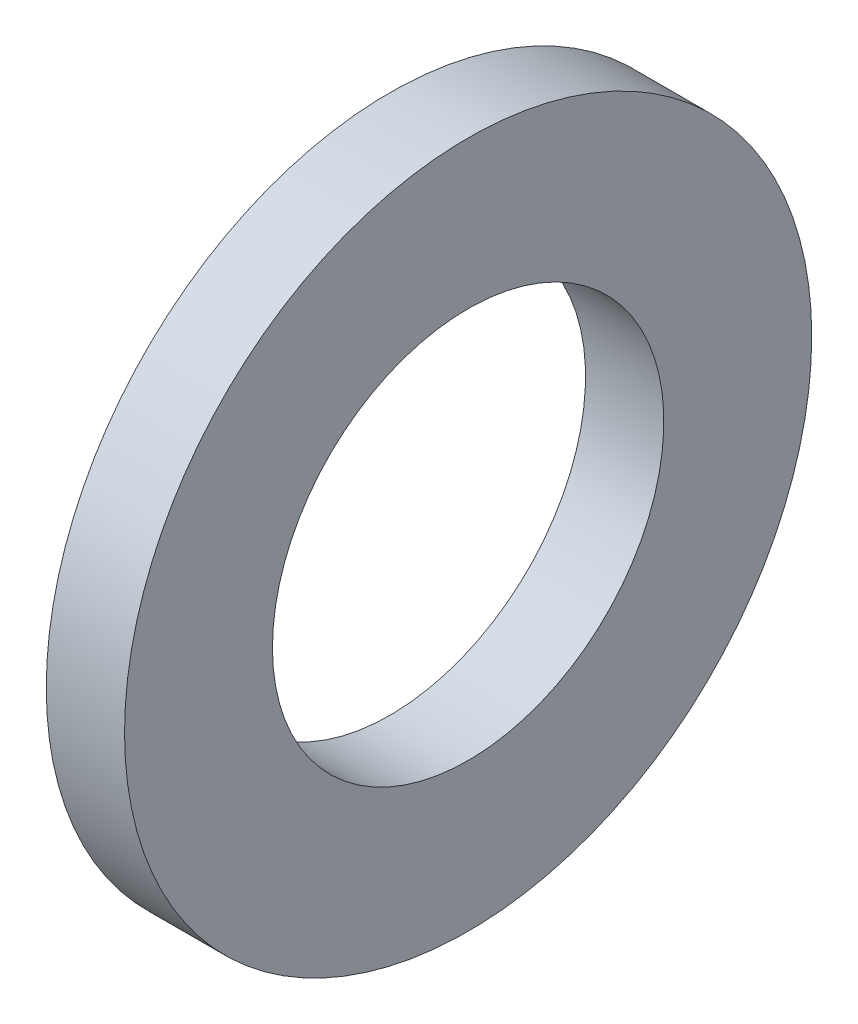
SolidWorks part; units mm, degrees
ref_plane "Front Plane" through (0, 0, 0) normal (0, 0, 1) x (1, 0, 0)
ref_plane "Top Plane" through (0, 0, 0) normal (0, 1, 0) x (1, 0, 0)
ref_plane "Right Plane" through (0, 0, 0) normal (1, 0, 0) x (0, 0, -1)
sketch "Sketch2" plane through (0, 0, 0) normal (0, 0, 1) x (1, 0, 0)
  line L0 (0, 0) -> (58.591, 0) construction
  line L2 (0, 0) -> (18.4, 0)
  line L3 (0, 0) -> (0, 2.5)
  line L4 (0, 2.5) -> (18.4, 2.5)
  line L5 (18.4, 0) -> (18.4, 2.5)
  line L6 (6.0094, 2.5) -> (6.0094, 6)
  line L11 (6.0094, 6) -> (9.9794, 6)
  line L16 (12.9794, 6) -> (12.9794, 3)
  line L17 (12.9794, 3) -> (13.6398, 3)
  line L18 (13.6398, 3) -> (13.6398, 2.5)
  line L19 (13.6398, 2.5) -> (6.0094, 2.5)
  line L22 (13.6398, 2.5) -> (16.1198, 2.5)
  line L23 (13.6398, 2.5) -> (13.6398, 4)
  line L24 (13.6398, 4) -> (16.1198, 4)
  line L25 (16.1198, 2.5) -> (16.1198, 4)
  line L27 (6.0094, 6) -> (9.9794, 6)
  line L28 (6.0094, 6) -> (6.0094, 9)
  line L29 (6.0094, 9) -> (9.9794, 9)
  line L30 (9.9794, 6) -> (9.9794, 9)
  line L31 (6.0094, 9) -> (6.0094, 8.25)
  line L32 (6.0094, 8.25) -> (5.0094, 8.25)
  line L33 (8.6609, 22.001) -> (8.6609, 12.476) construction
  line L34 (5.0094, 12.476) -> (12.3124, 12.476)
  line L35 (9.9794, 9) -> (12.3124, 9)
  line L36 (5.0094, 7.9375) -> (1.8344, 7.9375)
  line L37 (5.0094, 8.25) -> (5.0094, 12.476)
  line L38 (5.0094, 7.9375) -> (5.0094, 13.9365)
  line L39 (5.0094, 13.9365) -> (1.8344, 13.9365)
  line L40 (1.8344, 7.9375) -> (1.8344, 13.9365)
  line L41 (5.0094, 22.001) -> (12.3124, 22.001)
  line L42 (5.0094, 22.001) -> (5.0094, 30.1625)
  line L43 (5.0094, 30.1625) -> (12.3124, 30.1625)
  line L44 (12.3124, 22.001) -> (12.3124, 30.1625)
  line L49 (16.6398, 22.001) -> (16.6398, 7.5)
  line L51 (23.0198, 7.5) -> (23.0198, 6.5)
  line L54 (16.1198, 4) -> (13.6398, 4)
  line L56 (18.0398, 7.5) -> (23.0198, 7.5)
  line L57 (13.3124, 22.001) -> (16.6398, 22.001)
  line L58 (16.1198, 3.5) -> (20.0198, 3.5)
  line L59 (29.9098, 14) -> (26.9098, 11)
  line L60 (4.0094, 31.75) -> (18.0398, 31.75)
  line L61 (18.0398, 7.5) -> (23.0198, 7.5)
  line L62 (18.0398, 7.5) -> (18.0398, 12)
  line L63 (18.0398, 12) -> (23.0198, 12)
  line L64 (23.0198, 7.5) -> (23.0198, 12)
  line L65 (18.0398, 31.75) -> (18.0398, 12)
  line L66 (23.0198, 11) -> (26.9098, 11)
  line L67 (34.8098, 23) -> (31.3098, 19.5)
  line L68 (35.8098, 31) -> (38.7998, 33.99)
  line L69 (29.9098, 14) -> (29.9098, 15)
  line L70 (29.9098, 15) -> (22.9398, 15)
  line L71 (22.9398, 15) -> (21.0398, 15)
  line L72 (18.0398, 7.5) -> (16.6398, 7.5)
  line L73 (21.0398, 15) -> (21.0398, 43)
  line L74 (19.5798, 40) -> (9.6198, 40)
  line L75 (9.6198, 40) -> (4.0094, 40)
  line L76 (21.0398, 43) -> (19.5798, 43)
  line L77 (22.9398, 15) -> (29.9098, 15)
  line L78 (22.9398, 15) -> (22.9398, 21)
  line L79 (22.9398, 21) -> (29.9098, 21)
  line L80 (29.9098, 15) -> (29.9098, 21)
  line L81 (9.6198, 40) -> (19.5798, 40)
  line L82 (9.6198, 40) -> (9.6198, 50)
  line L83 (9.6198, 50) -> (19.5798, 50)
  line L84 (19.5798, 40) -> (19.5798, 50)
  line L85 (4.0094, 40) -> (4.0094, 31.75)
  line L86 (12.9794, 3) -> (12.9794, 2.5)
  line L87 (31.3098, 19.5) -> (29.9098, 19.5)
  line L88 (21.4694, 63.5) -> (21.4694, 51.308)
  line L89 (21.4694, 63.5) -> (25.9398, 63.5)
  line L90 (25.9398, 63.5) -> (25.9398, 25)
  line L91 (27.8398, 25) -> (25.9398, 25)
  line L92 (9.6198, 48) -> (8.1598, 48)
  line L93 (8.1598, 48) -> (8.1598, 53.476)
  line L94 (8.1598, 53.476) -> (19.5798, 53.476)
  line L95 (19.5798, 53.476) -> (19.5798, 50)
  line L96 (13.8698, 63.001) -> (13.8698, 53.476) construction
  line L97 (8.1598, 63.001) -> (19.5798, 63.001)
  line L98 (8.1598, 63.001) -> (8.1598, 68.2625)
  line L99 (8.1598, 68.2625) -> (19.5798, 68.2625)
  line L100 (19.5798, 63.001) -> (19.5798, 68.2625)
  line L101 (12.9794, 6) -> (11.9794, 6)
  line L102 (8.1598, 44.825) -> (4.9848, 44.825)
  line L103 (8.1598, 44.825) -> (8.1598, 54.9365)
  line L104 (8.1598, 54.9365) -> (4.9848, 54.9365)
  line L106 (9.9794, 6) -> (10.8794, 6)
  line L107 (27.8398, 25) -> (34.8098, 25)
  line L108 (34.8098, 25) -> (34.8098, 23)
  line L109 (0, 0) -> (-2, 0)
  line L110 (0, 0) -> (0, 11)
  line L111 (27.8398, 25) -> (34.8098, 25)
  line L112 (27.8398, 25) -> (27.8398, 32.5)
  line L113 (27.8398, 32.5) -> (34.8098, 32.5)
  line L114 (34.8098, 25) -> (34.8098, 32.5)
  line L115 (35.8098, 31) -> (34.8098, 31)
  line L116 (27.8398, 32.5) -> (27.8398, 64.5)
  line L117 (20.5373, 74.025) -> (6.2023, 74.025)
  line L118 (6.2023, 74.025) -> (6.2023, 76.2)
  line L119 (38.7998, 47.29) -> (30.8398, 55.25)
  line L120 (0, 11) -> (-2, 11)
  line L121 (38.7998, 43.815) -> (30.8623, 43.815)
  line L123 (-4.8152, 69.85) -> (1.5348, 76.2)
  line L124 (38.7998, 47.29) -> (38.7998, 33.99)
  line L125 (-2, 0) -> (-2, 11)
  line L126 (38.7998, 37.465) -> (30.8623, 37.465)
  line L127 (30.8623, 43.815) -> (30.8623, 37.465)
  line L128 (6.0094, 2.5) -> (6.0094, 0)
  line L129 (-0.0152, 63.5) -> (-0.0152, 30)
  line L132 (4.9848, 63.5) -> (-0.0152, 63.5)
  line L136 (-1.8152, 30) -> (-11.7752, 30)
  line L138 (-13.7752, 25.4) -> (-2, 25.4)
  line L139 (-2, 25.4) -> (-2, 11.5)
  line L140 (27.8398, 64.5) -> (20.5373, 64.5)
  line L141 (-1.8152, 30) -> (-11.7752, 30)
  line L142 (-1.8152, 30) -> (-1.8152, 39)
  line L143 (-1.8152, 39) -> (-11.7752, 39)
  line L144 (-11.7752, 30) -> (-11.7752, 39)
  line L145 (20.5373, 64.5) -> (20.5373, 74.025)
  line L146 (-12.7752, 37) -> (-12.7752, 47.29)
  line L147 (-12.7752, 37) -> (-11.7752, 37)
  line L148 (30.8398, 55.25) -> (30.8398, 76.2)
  line L149 (11.9794, 6) -> (11.9794, 5.45)
  line L154 (-2, 11.5) -> (0.5, 11.5)
  line L155 (4.9848, 60.6197) -> (24.0348, 60.6197)
  line L160 (4.9848, 60.6197) -> (4.9848, 55.8572)
  line L161 (4.9848, 55.8572) -> (24.0348, 55.8572)
  line L166 (24.0348, 60.6197) -> (24.0348, 55.8572)
  line L167 (4.9848, 60.6197) -> (24.0348, 55.8572) construction
  line L172 (4.9848, 55.8572) -> (24.0348, 60.6197) construction
  line L173 (24.0348, 62.2072) -> (25.9398, 62.2072)
  line L174 (11.9794, 5.45) -> (10.8794, 5.45)
  line L175 (10.8794, 6) -> (10.8794, 5.45)
  line L176 (24.0348, 62.2072) -> (24.0348, 54.2697)
  line L177 (24.0348, 54.2697) -> (25.9398, 54.2697)
  line L178 (25.9398, 62.2072) -> (25.9398, 54.2697)
  line L179 (24.0348, 62.2072) -> (25.9398, 54.2697) construction
  line L180 (24.0348, 54.2697) -> (25.9398, 62.2072) construction
  line L181 (3, 19.6197) -> (15.7, 19.6197)
  line L182 (3, 19.6197) -> (3, 14.8572)
  line L183 (3, 14.8572) -> (15.7, 14.8572)
  line L184 (15.7, 19.6197) -> (15.7, 14.8572)
  line L185 (3, 19.6197) -> (15.7, 14.8572) construction
  line L186 (3, 14.8572) -> (15.7, 19.6197) construction
  line L187 (15.7, 21.2072) -> (16.6398, 21.2072)
  line L188 (15.7, 21.2072) -> (15.7, 13.2697)
  line L189 (15.7, 13.2697) -> (16.6398, 13.2697)
  line L190 (16.6398, 21.2072) -> (16.6398, 13.2697)
  line L191 (15.7, 21.2072) -> (16.6398, 13.2697) construction
  line L192 (15.7, 13.2697) -> (16.6398, 21.2072) construction
  line L193 (0.5, 11.5) -> (0.5, 6.9375)
  line L194 (0.5, 6.9375) -> (1.8344, 6.9375)
  line L195 (23.0198, 6.5) -> (20.0198, 3.5)
  line L196 (4.9848, 63.5) -> (4.9848, 54.9365)
  line L197 (3, 43.825) -> (4.9848, 43.825)
  line L198 (1.8344, 6.9375) -> (1.8344, 7.9375)
  line L199 (6.0094, 0) -> (12.9794, 0)
  line L200 (12.9794, 0) -> (12.9794, 2.5)
  line L201 (18.0398, 31.75) -> (18.0398, 35.875)
  line L202 (18.0398, 35.875) -> (21.0398, 35.875)
  line L203 (30.8398, 76.2) -> (6.2023, 76.2)
  line L204 (2.7573, 69.85) -> (7.2023, 69.85) construction
  line L205 (7.2023, 67.4688) -> (26.2523, 67.4688)
  line L206 (7.2023, 74.025) -> (7.2023, 64.5)
  line L207 (7.2023, 64.5) -> (-1.8152, 64.5)
  line L208 (-1.8152, 64.5) -> (-1.8152, 39)
  line L209 (-12.7752, 47.29) -> (-4.8152, 55.25)
  line L210 (-4.8152, 55.25) -> (-4.8152, 69.85)
  line L211 (7.2023, 67.4688) -> (7.2023, 72.2312)
  line L212 (7.2023, 72.2312) -> (26.2523, 72.2313)
  line L213 (26.2523, 67.4688) -> (26.2523, 72.2313)
  line L214 (26.2523, 73.8187) -> (30.8398, 73.8187)
  line L215 (26.2523, 73.8187) -> (26.2523, 65.8813)
  line L216 (26.2523, 65.8813) -> (30.8398, 65.8813)
  line L217 (30.8398, 73.8187) -> (30.8398, 65.8813)
  line L218 (2.7573, 72.2313) -> (24.9823, 72.2313)
  line L219 (2.7573, 72.2313) -> (2.7573, 67.4687)
  line L220 (2.7573, 67.4687) -> (24.9823, 67.4687)
  line L221 (24.9823, 72.2313) -> (24.9823, 67.4687)
  line L222 (24.9823, 69.85) -> (20.5373, 69.85) construction
  line L223 (21.4694, 51.308) -> (22.9398, 51.308)
  line L224 (22.9398, 51.308) -> (22.9398, 21)
  line L225 (13.6398, 4) -> (13.6398, 12.2697)
  line L226 (13.6398, 12.2697) -> (13.3124, 12.2697)
  line L227 (13.3124, 12.2697) -> (13.3124, 22.001)
  line L228 (12.3124, 9) -> (12.3124, 12.476)
  line L229 (-1.8152, 30) -> (-0.0152, 30)
  line L230 (8.1598, 65.6317) -> (2.7573, 65.6317) construction
  line L231 (19.5798, 65.6317) -> (24.9823, 65.6317) construction
  line L232 (1.5348, 76.2) -> (6.2023, 76.2)
  line L233 (-11.7752, 30) -> (-13.7752, 30)
  line L234 (-13.7752, 30) -> (-13.7752, 25.4)
  line L235 (3, 13.9365) -> (3, 43.825)
  line L236 (4.9848, 54.9365) -> (4.9848, 44.825)
  line L237 (4.9848, 43.825) -> (4.9848, 44.825)
  circle A0 centre (26.8898, 25.95) radius 0.95
  circle A1 centre (21.9898, 15.95) radius 0.95
  circle A2 centre (17.3398, 8.2) radius 0.7
  circle A3 centre (10.4294, 6.45) radius 0.45
  circle A4 centre (-0.9152, 30.9) radius 0.9
  point P7 (24.9873, 58.2385)
  point P131 (16.1699, 17.2385)
  point P135 (14.5098, 58.2385)
  point P146 (9.35, 17.2385)
sketch "Sketch3" plane through (0, 0, 0) normal (0, 0, 1) x (1, 0, 0)
  line L0 (5.0094, 7.9375) -> (5.0094, 13.9365) construction
  line L1 (5.0094, 13.9365) -> (1.8344, 13.9365) construction
  line L2 (1.8344, 7.9375) -> (1.8344, 13.9365) construction
  line L3 (5.0094, 7.9375) -> (1.8344, 7.9375) construction
  line L4 (5.0094, 7.9375) -> (5.0094, 13.9365)
  line L5 (5.0094, 13.9365) -> (1.8344, 13.9365)
  line L6 (1.8344, 7.9375) -> (1.8344, 13.9365)
  line L7 (5.0094, 7.9375) -> (1.8344, 7.9375)
revolve "Revolve1" add sketch "Sketch3" angle 360 about L0
